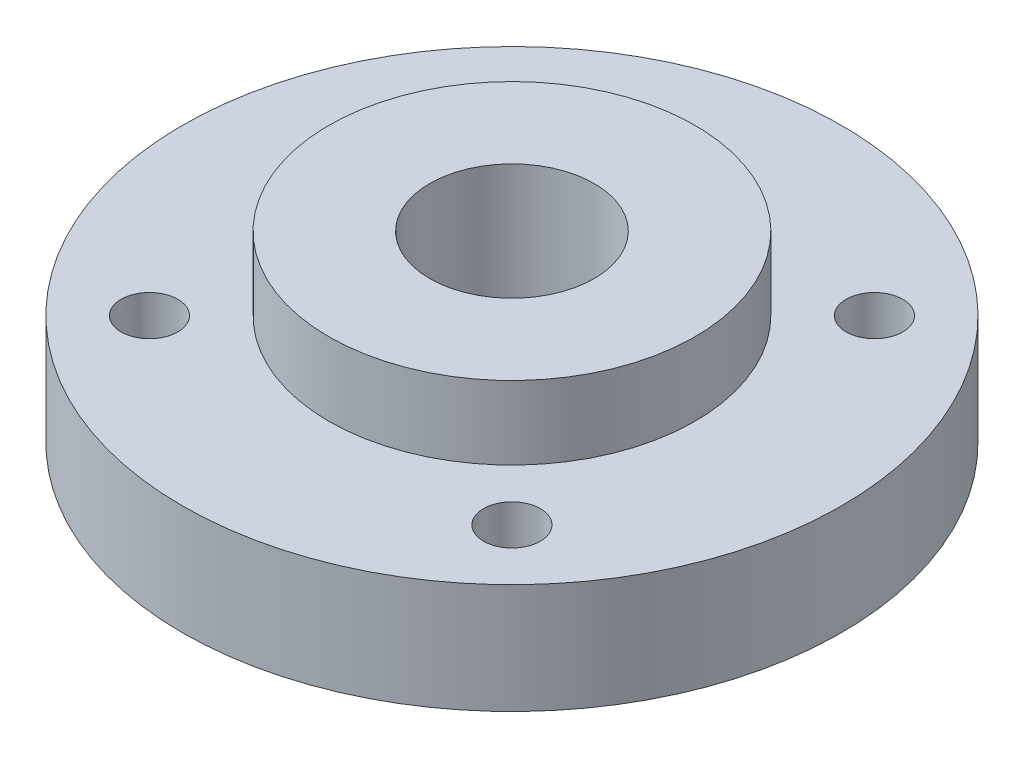
SolidWorks part; units mm, degrees
material "6061-T6 (SS)"
ref_plane "Front Plane" through (0, 0, 0) normal (0, 0, 1) x (1, 0, 0)
ref_plane "Top Plane" through (0, 0, 0) normal (0, 1, 0) x (1, 0, 0)
ref_plane "Right Plane" through (0, 0, 0) normal (1, 0, 0) x (0, 0, -1)
sketch "Sketch1" plane through (0, 0, 0) normal (0, 0, 1) x (1, 0, 0)
  line L0 (0, 0) -> (0, -14.566) construction
  line L6 (-11.1125, -73.8302) -> (-11.1125, -77.0052)
  line L7 (-15.875, -57.9552) -> (-15.875, -64.3052)
  line L8 (-15.875, -64.3052) -> (-28.575, -64.3052)
  line L9 (-28.575, -64.3052) -> (-28.575, -73.8302)
  line L12 (76.2, -73.8302) -> (-76.2, -73.8302) construction
  line L14 (-14.2875, -73.8302) -> (-14.2875, -77.0052)
  line L15 (-14.2875, -77.0052) -> (-11.1125, -77.0052)
  line L17 (-28.575, -73.8302) -> (-19.05, -73.8302)
  line L18 (-19.05, -73.8302) -> (-19.05, -70.6933)
  line L19 (-19.05, -70.6933) -> (-14.2875, -70.6933)
  line L20 (-14.2875, -70.6933) -> (-14.2875, -73.8302)
  line L21 (-15.875, -57.9552) -> (-4.7625, -57.9552)
  line L22 (-4.7625, -57.9552) -> (-4.7625, -73.8302)
  line L23 (-4.7625, -73.8302) -> (-11.1125, -73.8302)
  point P1 (0, 0)
  point P12 (0, -94.0625)
  point P13 (-15.875, -57.3118)
  point P17 (-15.875, -57.9552)
  point P19 (0, 0)
  point P22 (0, 0)
  point P23 (0, 0)
  point P24 (0, -14.566)
  dimension "D2" = 3.175
  dimension "D3" = 9.525
  dimension "D4" = 9.525
  dimension "D5" = 3.175
  dimension "D6" = 12.7
  dimension "D7" = 57.15
  dimension "D8" = 15.875
  dimension "D9" = 28.575
  dimension "D11" = 3.175
  dimension "D12" = 38.1
  dimension "D13" = 3.1369
revolve "Revolve1" add sketch "Sketch1" angle 360 about L0
hole_wizard "#10 (0.1935) Diameter Hole1" positions "Sketch2" profile "Sketch3" hole size "#10" standard "ANSI Inch" end condition through all
sketch "Sketch2" plane through (0, -57.9552, 0) normal (0, 1, 0) x (1, 0, 0)
  line L0 (-15.7154, 15.7154) -> (15.7154, -15.7154) construction
  line L2 (15.7154, 15.7154) -> (-15.7154, -15.7154) construction
  line L3 (0, 0) -> (-24.6236, 0) construction
  point P0 (15.7154, 15.7154)
  point P2 (-15.7154, 15.7154)
  point P4 (-15.7154, -15.7154)
  point P6 (15.7154, -15.7154)
  point P25 (-24.6236, 0)
  point P26 (0, 0)
  dimension "D1" = 44.45
  dimension "D2" = 45
sketch "Sketch3" plane through (15.7154, -57.9552, -15.7154) normal (1, 0, 0) x (0, 0, 1)
  line L0 (0, 0) -> (0, 19.05)
  line L1 (0, 19.05) -> (2.4574, 19.05)
  line L2 (2.4574, 19.05) -> (2.4574, 0)
  line L5 (2.4574, 0) -> (0, 0)
  line L11 (0, -6.35) -> (0, 107.95) construction
  dimension "Thru Hole Dia." = 4.9149
  dimension "Thru Hole Depth" = 19.05
hole_wizard "Pipe Tap Drill for 3/8 Tap1" positions "3DSketch1" profile "Sketch4" hole size "3/8" standard "ANSI Inch"
sketch3d "3DSketch1"
  circle A1 centre (0, -57.9552, 0) radius 15.875 construction
  point P0 (0, -57.9552, 0)
  point P6 (0, 0, 0)
  point P9 (0, -42.0802, 0)
  point P10 (0, 0, 0)
sketch "Sketch4" plane through (0, -57.9552, 0) normal (1, 0, 0) x (0, 0, 1)
  line L0 (0, 0) -> (0, 16.9886)
  line L1 (0, 16.9886) -> (7.1374, 12.7)
  line L2 (7.1374, 12.7) -> (7.1374, 0)
  line L5 (7.1374, 0) -> (0, 0)
  line L10 (0, 16.9886) -> (-7.1374, 12.7) construction
  line L11 (0, -6.35) -> (0, 107.95) construction
  dimension "Hole Dia." = 14.2748
  dimension "Hole Depth" = 12.7
  dimension "Drill Angle" = 118
